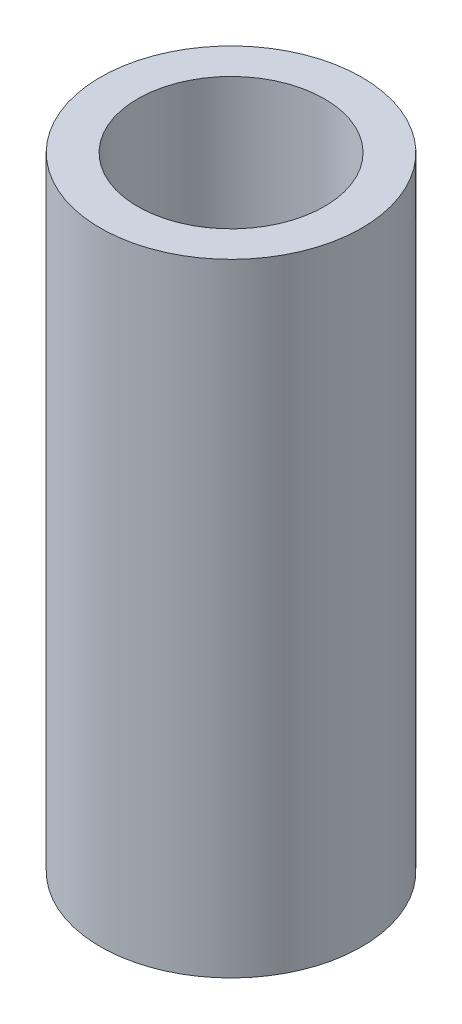
SolidWorks part; units mm, degrees
material "Custom Plastic"
ref_plane "Front Plane" through (0, 0, 0) normal (0, 0, 1) x (1, 0, 0)
ref_plane "Top Plane" through (0, 0, 0) normal (0, 1, 0) x (1, 0, 0)
ref_plane "Right Plane" through (0, 0, 0) normal (1, 0, 0) x (0, 0, -1)
sketch "Sketch1" plane through (0, 0, 0) normal (0, 0, 1) x (1, 0, 0)
  line L0 (0, 0) -> (0, 11.3889) construction
  line L2 (-1.5, 0) -> (-2.1, 0)
  line L3 (-1.5, 0) -> (-1.5, 10)
  line L4 (-1.5, 10) -> (-2.1, 10)
  line L5 (-2.1, 0) -> (-2.1, 10)
  dimension "D1" = 3
  dimension "D2" = 0.6
  dimension "D3" = 10
revolve "Revolve1" add sketch "Sketch1" angle 360 about L0
